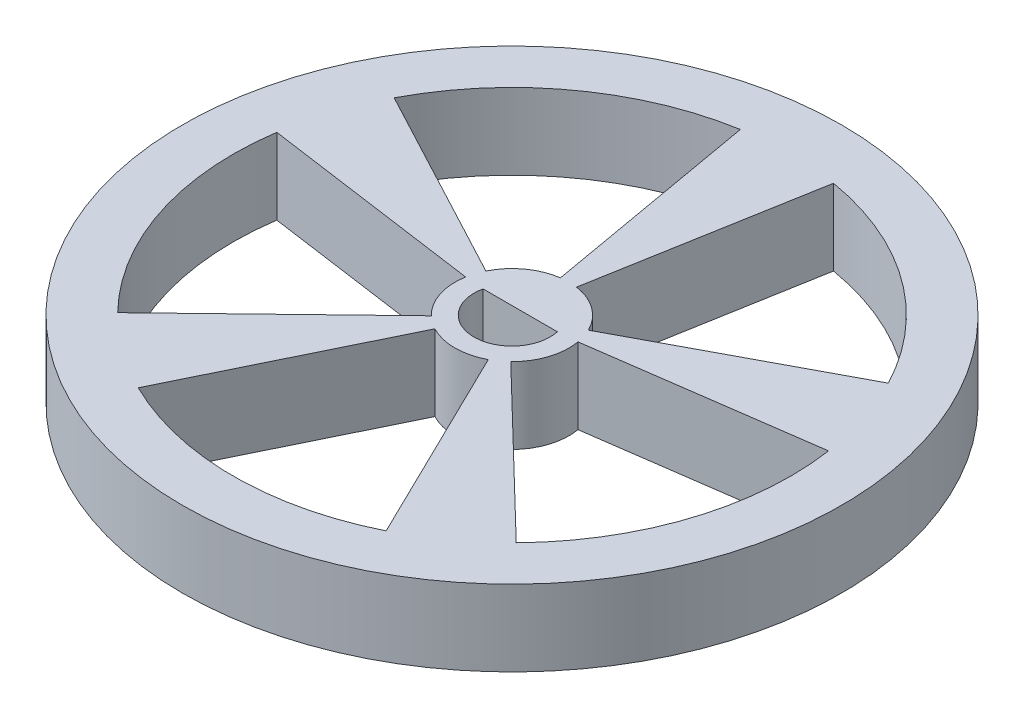
SolidWorks part; units mm, degrees
ref_plane "Front Plane" through (0, 0, 0) normal (0, 0, 1) x (1, 0, 0)
ref_plane "Top Plane" through (0, 0, 0) normal (0, 1, 0) x (1, 0, 0)
ref_plane "Right Plane" through (0, 0, 0) normal (1, 0, 0) x (0, 0, -1)
sketch "Sketch1" plane through (0, 0, 0) normal (0, 1, 0) x (1, 0, 0)
  line L0 (0, 3) -> (2.438, 3) construction
  line L1 (-2.9287, 0.65) -> (2.9287, 0.65)
  line L2 (0, 4.5) -> (0, 26) construction
  line L3 (-4.3688, 25.6303) -> (-0.635, 4.455)
  line L4 (4.2437, 25.2463) -> (4.3688, 25.6303)
  line L5 (4.3688, 25.6303) -> (0.635, 4.455)
  line L6 (23.0259, 12.0752) -> (4.0407, 1.9806)
  line L7 (25.7259, 3.7652) -> (4.4332, 0.7727)
  line L8 (18.5996, -18.1675) -> (3.1323, -3.2309)
  line L9 (11.5307, -23.3033) -> (2.1048, -3.9774)
  line L10 (-11.5307, -23.3033) -> (-2.1048, -3.9774)
  line L11 (-18.5996, -18.1675) -> (-3.1323, -3.2309)
  line L12 (-25.7259, 3.7652) -> (-4.4332, 0.7727)
  line L13 (-23.0259, 12.0752) -> (-4.0407, 1.9806)
  circle A0 centre (0, 0) radius 3
  circle A1 centre (0, 0) radius 4.5
  circle A2 centre (0, 0) radius 26
  circle A3 centre (0, 0) radius 22
  point P35 (0, 0)
  dimension "D1" = 2.35
  dimension "D2" = 10
  dimension "D3" = 10
  dimension "D4" = 0.635
  dimension "D5" = 0.635
  dimension "D6" = 5
extrude "Boss-Extrude1" add sketch "Sketch1" along normal blind 6 contours A3 L3 A2 L13 | A3 L13 A2 L12 | A3 L12 A2 L11 | A3 L11 A2 L10 | A3 L10 A2 L9 | A3 L9 A2 L8 | A3 L8 A2 L7 | A3 L7 A2 L6 | A3 L6 A2 L5 | A3 L5 A2 L3 | L5 A3 L3 A1 | L7 A3 L6 A1 | L9 A3 L8 A1 | L11 A3 L10 A1 | L13 A3 L12 A1 | A1 A0 | L1 A0 region at (0, 0, -1.6311) region at (0, 0, -23.9441) region at (-13.6458, 0, -18.7818) region at (0, 0, -15.2388) region at (13.6458, 0, -18.7818) region at (-22.7722, 0, -7.3991) region at (0, 0, -4.3727) region at (-14.4929, 0, -4.709) region at (22.7722, 0, -7.3991) region at (-22.0793, 0, 7.174) region at (14.4929, 0, -4.709) region at (22.0793, 0, 7.174) region at (-14.074, 0, 19.3712) region at (-8.9571, 0, 12.3284) region at (0, 0, 23.2156) region at (14.074, 0, 19.3712) region at (8.9571, 0, 12.3284)
extrude "Boss-Extrude2" add sketch "Sketch1<4>" along normal blind 0.6 contours A0
sketch "Sketch1<4>" plane through (0, 0, 0) normal (0, 1, 0) x (1, 0, 0) same geometry as "Sketch1"
